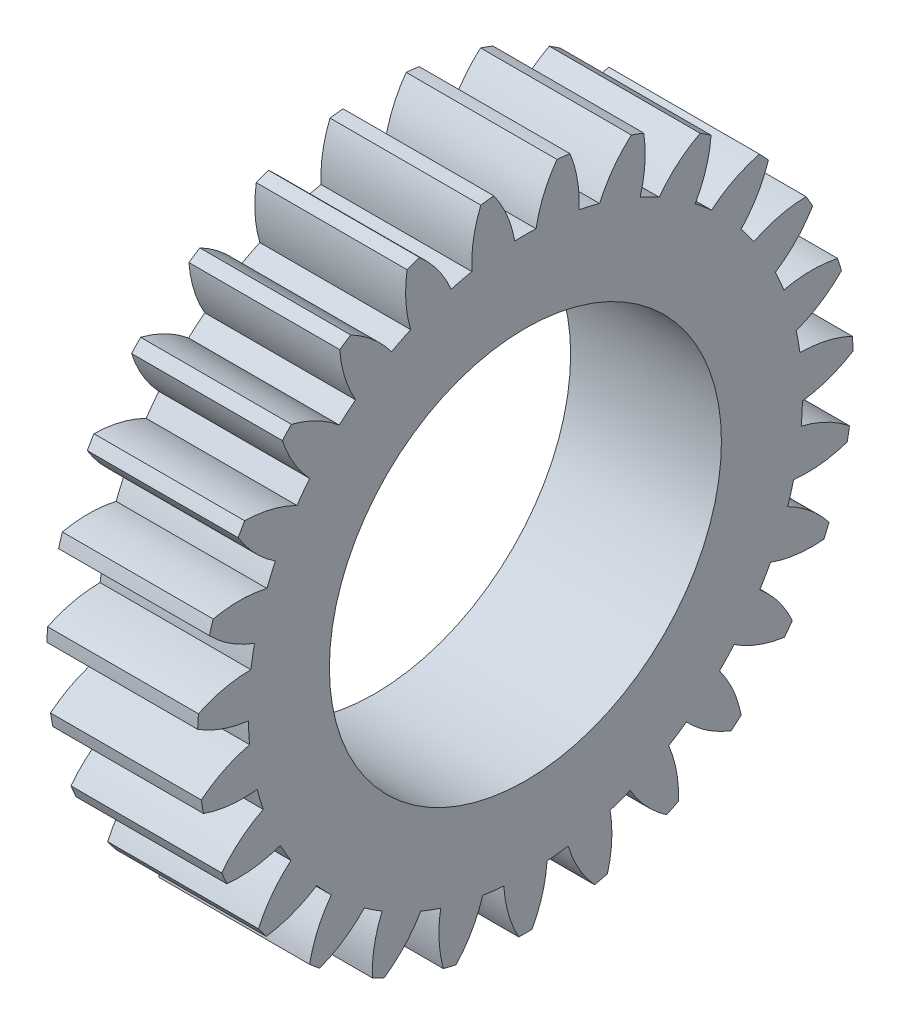
SolidWorks part; units mm, degrees
material "7075-O (SS)"
ref_plane "Plane1" through (0, 0, 0) normal (0, 0, 1) x (1, 0, 0)
ref_plane "Plane2" through (0, 0, 0) normal (0, 1, 0) x (1, 0, 0)
ref_plane "Plane3" through (0, 0, 0) normal (1, 0, 0) x (0, 0, -1)
sketch "HoldingSke" plane through (0, 0, 0) normal (0, 1, 0) x (1, 0, 0)
  line L0 (0, 0) -> (0.594, -0.3027)
  line L1 (-15, 0) -> (100, 0) construction
  line L2 (0, 0) -> (-2.1039, 2.3779)
  line L3 (0, 0) -> (-11.863, 4.5341)
  line L4 (0, 0) -> (7.6947, 3.9207)
  line L5 (0, 0) -> (-46.8476, -17.4728)
  line L6 (0, 0) -> (-8.2896, -5.593)
  line L7 (-2.1039, 2.3779) -> (8.6586, 51.2059)
  line L8 (-76.2, 54.61) -> (-72.9, 54.61)
  line L9 (-71.009, 38.7566) -> (-53.1078, 45.2721)
  line L10 (-76.2, 71.12) -> (104.1128, 71.12)
  line L11 (0, 0) -> (-10, 0)
  line L12 (-76.2, 101.6) -> (-76.147, 101.6)
  line L13 (24.9733, 27.94) -> (52.9518, 28.4284)
  line L14 (24.9733, 27.94) -> (24.9743, 27.94)
  line L15 (24.9733, 27.94) -> (100.4006, 29.5858)
  line L16 (-63.627, -1.5) -> (-12.827, -1.5)
  circle A0 centre (0, 0) radius 13
  circle A1 centre (0, 0) radius 18.374
  circle A2 centre (0, 0) radius 37.5
  circle A3 centre (0, 0) radius 13
  dimension "Num_teeth" = 27
  dimension "Pitch_radius" = 180.3128
  dimension "Width" = 10
  dimension "Thickness" = 10
sketch "BasProSke" plane through (0, 0, 0) normal (0, 1, 0) x (1, 0, 0)
  line L0 (-10, 0) -> (60, 0) construction
  line L1 (0, 0) -> (0, 21.75)
  line L2 (0, 0) -> (10, 0)
  line L3 (10, 0) -> (10, 21.75)
  line L4 (10, 21.75) -> (0, 21.75)
  dimension "Thickness" = 10
  dimension "Diameter" = 43.5
revolve "Base-Revolve" add sketch "BasProSke" angle 360 about L0
sketch "TooCutSke" plane through (0, 0, 0) normal (1, 0, 0) x (0, 0, -1)
  line L1 (0, 0) -> (0, 107) construction
  line L2 (0, 0) -> (-1.2702, 20.2101) construction
  line L3 (0, 0) -> (-4.695, 40.1684) construction
  line L4 (-1.2702, 20.2101) -> (-2.3475, 20.0842) construction
  arc A0 (0.7048, 18.3605) -> (-0.7048, 18.3605) centre (0, 0) ccw
  arc A1 (2.1089, 21.673) -> (-2.1089, 21.673) centre (0, 0) ccw
  circle A2 centre (0, 0) radius 20.25 construction
  circle A3 centre (0, 0) radius 19.0288 construction
  arc A4 (-0.7048, 18.3605) -> (-2.1089, 21.673) centre (-8.6783, 16.9346) ccw
  arc A5 (2.1089, 21.673) -> (0.7048, 18.3605) centre (8.6783, 16.9346) ccw
extrude "ToothCut" cut sketch "TooCutSke" along normal through all
fillet "Breaks" [suppressed] radius 0.03 tangent propagation no
fillet "RootFillets" [suppressed] radius 0.376
pattern_circular "TeethCuts" count 27 every 13.333 about axis through (-10, 0, 0) along (1, 0, 0) of "ToothCut", "RootFillets", "Breaks"
sketch "HubNeaOneSke" plane through (0, 0, 0) normal (-1, 0, 0) x (0, 0, 1)
  circle A0 centre (0, 0) radius 18.374
  dimension "Diameter" = 36.748
extrude "HubNearOne" [suppressed] add sketch "HubNeaOneSke" along normal blind 40.0001
sketch "HubNeaBotSke" plane through (0, 0, 0) normal (-1, 0, 0) x (0, 0, 1)
  circle A0 centre (0, 0) radius 18.374
  dimension "Diameter" = 36.748
extrude "HubNearBoth" [suppressed] add sketch "HubNeaBotSke" along normal blind 20
ref_plane "FarPln" through (10, 0, 0) normal (1, 0, 0) x (0, 0, -1)
sketch "HubFarSke" plane through (10, 0, 0) normal (1, 0, 0) x (0, 0, -1)
  circle A0 centre (0, 0) radius 18.374
  dimension "Diameter" = 36.748
extrude "HubFar" [suppressed] add sketch "HubFarSke" along normal blind 20
sketch "BorSke" plane through (0, 0, 0) normal (1, 0, 0) x (0, 0, -1)
  circle A0 centre (0, 0) radius 13
  dimension "Diameter" = 26
extrude "Bore" cut sketch "BorSke" along normal mid plane 100.0001
sketch "KeySke" plane through (0, 0, 0) normal (1, 0, 0) x (0, 0, -1)
  line L0 (-4, 0) -> (-4, 16.3)
  line L1 (-4, 16.3) -> (4, 16.3)
  line L2 (4, 16.3) -> (4, 0)
  line L3 (0, 0) -> (0, 34) construction
  line L4 (-4, 0) -> (4, 0)
  dimension "Width" = 8
extrude "Keyway" [suppressed] cut sketch "KeySke" along normal mid plane 100.0001
pattern_circular "Keyway2" [suppressed] count 2 every 90 about axis through (-10, 0, 0) along (1, 0, 0) reverse direction yes
equation "' \"Module@HoldingSke\" = 6.35"
equation "' \"Num_teeth@HoldingSke\" = 12"
equation "' \"Ap@HoldingSke\" =  20"
equation "' \"Ap@HoldingSke\" = 20"
equation "' \"Width@HoldingSke\" = 0.5 * 25.4"
equation "' \"Hub_dia@HoldingSke\"= 1 * 25.4"
equation "' \"Hub_dia@HoldingSke\" = 1 * 25.4"
equation "' \"Overall_len@HoldingSke\" = 1.0 * 25.4"
equation "' \"Bore@HoldingSke\" = 0.75 * 25.4"
equation "' \"T_dim@HoldingSke\" = 0.1 * 25.4"
equation "' \"Width@KeySke\" = 0.25 * 25.4"
equation "' \"Show_teeth@HoldingSke\" = 13"
equation "' \"Backlash@HoldingSke\" = 0.009 * 25.4"
equation "' \"Addendum_fac@HoldingSke\" = 1.0"
equation "' \"Dedendum_fac@HoldingSke\" = 1.25"
equation "' \"Dedendum_add@HoldingSke\" = 0.00005 * 25.4"
equation "' \"Clearance_fac@HoldingSke\" = 0.25"
equation "\"Pitch@HoldingSke\" = 1 / \"Module@HoldingSke\""
equation "\"Overcut_dia@TooCutSke\" = (\"Num_teeth@HoldingSke\" + 2 * \"Addendum_fac@HoldingSke\") / \"Pitch@HoldingSke\" + 0.002 * 25.4"
equation "\"Pitch_dia@TooCutSke\" = \"Num_teeth@HoldingSke\" / \"Pitch@HoldingSke\""
equation "\"Base_dia@TooCutSke\" = \"Num_teeth@HoldingSke\" / \"Pitch@HoldingSke\" * cos((\"Ap@HoldingSke\"  * 3.14159265 / 180))"
equation "\"Root_dia@TooCutSke\" = (\"Num_teeth@HoldingSke\" + 2) / \"Pitch@HoldingSke\" - 2 * (\"Addendum_fac@HoldingSke\" + \"Dedendum_fac@HoldingSke\") / \"Pitch@HoldingSke\" - \"Dedendum_add@HoldingSke\" * 2"
equation "\"Half_ang@TooCutSke\" = 180 / \"Num_teeth@HoldingSke\""
equation "\"Half_CT@TooCutSke\" = \"Num_teeth@HoldingSke\" / \"Pitch@HoldingSke\" * sin((3.14159265 / 2 / \"Num_teeth@HoldingSke\")) / 2 - 7 * \"Backlash@HoldingSke\" / 4"
equation "\"Flank_rad@TooCutSke\" = \"Num_teeth@HoldingSke\" / \"Pitch@HoldingSke\" / 5"
equation "\"Radius@RootFillets\" = \"Clearance_fac@HoldingSke\" / \"Pitch@HoldingSke\" + \"Dedendum_add@HoldingSke\""
equation "\"Break_rad@Breaks\" = 0.02 / \"Pitch@HoldingSke\""
equation "\"Thickness@HoldingSke\" = \"Width@HoldingSke\""
equation "\"OAL@HoldingSke\" = \"Thickness@HoldingSke\""
equation "\"MHD@HoldingSke\" = (\"Num_teeth@HoldingSke\" + 2) / \"Pitch@HoldingSke\" - 2 * (\"Addendum_fac@HoldingSke\" + \"Dedendum_fac@HoldingSke\")  / \"Pitch@HoldingSke\" - \"Dedendum_add@HoldingSke\" * 2"
equation "\"MBD@HoldingSke\" = (\"Num_teeth@HoldingSke\" + 2) / \"Pitch@HoldingSke\" - 2 * (\"Addendum_fac@HoldingSke\" + \"Dedendum_fac@HoldingSke\")  / \"Pitch@HoldingSke\" - \"Dedendum_add@HoldingSke\" * 2 - 0.002 * 25.4"
equation "\"MHD@HoldingSke\" = ((sgn( \"MHD@HoldingSke\" - \"Hub_dia@HoldingSke\" )-1)*( \"MHD@HoldingSke\" - \"Hub_dia@HoldingSke\" ))/-2+ \"Hub_dia@HoldingSke\""
equation "\"MBD@HoldingSke\" = ((sgn( \"MBD@HoldingSke\" - \"Bore@HoldingSke\" )-1)*( \"MBD@HoldingSke\" - \"Bore@HoldingSke\" ))/-2+ \"Bore@HoldingSke\""
equation "\"OAL@HoldingSke\" = ((sgn( \"OAL@HoldingSke\" - \"Overall_len@HoldingSke\" )+1)*( \"OAL@HoldingSke\" - \"Overall_len@HoldingSke\" ))/2 + \"Overall_len@HoldingSke\" + 0.000002 * 25.4"
equation "\"Num_teeth@TeethCuts\" = int( \"Show_teeth@HoldingSke\" ) + 1"
equation "\"Num_teeth@TeethCuts\" = ((sgn( \"Num_teeth@TeethCuts\" - \"Num_teeth@HoldingSke\" )-1)*( \"Num_teeth@TeethCuts\" - \"Num_teeth@HoldingSke\" ))/-2+ \"Num_teeth@HoldingSke\""
equation "\"Num_teeth@TeethCuts\" = ((sgn( \"Num_teeth@TeethCuts\" - 2.0)+1)*( \"Num_teeth@TeethCuts\" - 2.0))/2 +2.0"
equation "\"Angle@TeethCuts\" = 360.0 / \"Num_teeth@HoldingSke\""
equation "\"Diameter@BasProSke\" = (\"Num_teeth@HoldingSke\" + 2 * \"Addendum_fac@HoldingSke\") / \"Pitch@HoldingSke\""
equation "\"Thickness@BasProSke\"  = \"Thickness@HoldingSke\""
equation "' \"Fillet_rad@BasProSke\" =  \"Thickness@HoldingSke\" * 0.05"
equation "' \"Fillet_rad@BasProSke\" = \"Thickness@HoldingSke\" * 0.05"
equation "\"MHD@HoldingSke\" = ((sgn( \"MHD@HoldingSke\" - \"Root_dia@TooCutSke\" )-1)*( \"MHD@HoldingSke\" - \"Root_dia@TooCutSke\" ))/-2+ \"Root_dia@TooCutSke\""
equation "\"Diameter@HubNeaOneSke\" = \"MHD@HoldingSke\""
equation "\"Length@HubNearOne\" = \"OAL@HoldingSke\" - \"Thickness@BasProSke\""
equation "\"Diameter@HubNeaBotSke\" = \"MHD@HoldingSke\""
equation "\"Length@HubNearBoth\" = ( \"OAL@HoldingSke\" - \"Thickness@BasProSke\" ) / 2.0"
equation "\"Thickness@FarPln\" = \"Thickness@BasProSke\""
equation "\"Diameter@HubFarSke\" = \"MHD@HoldingSke\""
equation "\"Length@HubFar\" = ( \"OAL@HoldingSke\" - \"Thickness@BasProSke\" ) / 2.0"
equation "\"Diameter@BorSke\" = \"MBD@HoldingSke\""
equation "\"D1@Bore\" = \"OAL@HoldingSke\" * 2.0"
equation "\"D1@Keyway\" = \"OAL@HoldingSke\" * 2.0"
equation "\"Offset@KeySke\" = \"T_dim@HoldingSke\" + \"MBD@HoldingSke\" / 2.0"
